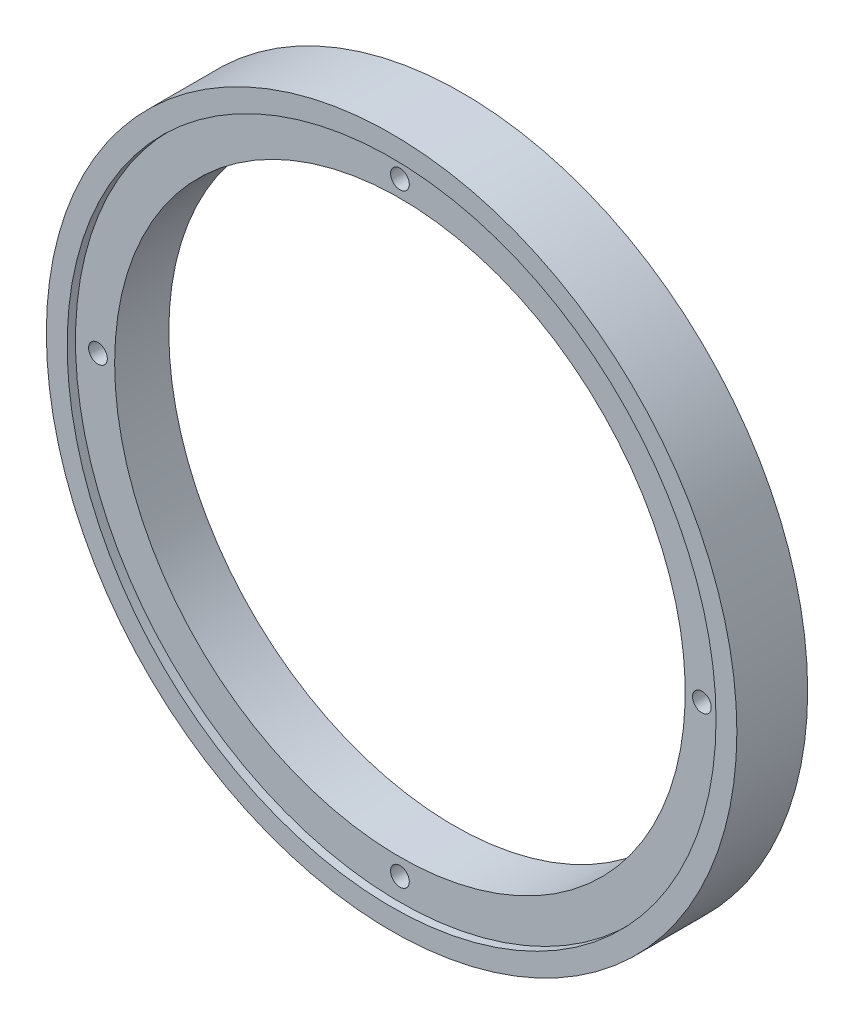
SolidWorks part; units mm, degrees
ref_plane "Plan de face" through (0, 0, 0) normal (0, 0, 1) x (1, 0, 0)
ref_plane "Plan de dessus" through (0, 0, 0) normal (0, 1, 0) x (1, 0, 0)
ref_plane "Plan de droite" through (0, 0, 0) normal (1, 0, 0) x (0, 0, -1)
sketch "Esquisse1" plane through (0, 0, 0) normal (0, 0, 1) x (1, 0, 0)
  line L14 (0, 72.5) -> (0, -72.5) construction
  line L15 (-72.5, 0) -> (72.5, 0) construction
  circle A60 centre (0, 0) radius 77.9
  circle A61 centre (0, 0) radius 72.5 construction
  circle A62 centre (0, 72.5) radius 2.25
  circle A63 centre (72.5, 0) radius 2.25
  circle A64 centre (0, -72.5) radius 2.25
  circle A65 centre (-72.5, 0) radius 2.25
  circle A66 centre (0, 0) radius 68.5
  point P0 (0, 0)
  point P30 (0, 0)
  point P52 (0, 0)
  point P57 (0, 0)
  point P83 (0, 0)
  point P105 (0, 0)
  dimension "D5" = 4.5
  dimension "D3" = 155.8
  dimension "D4" = 145
  dimension "D1" = 137
  dimension "D6" = 4
extrude "Boss.-Extru.1" add sketch "Esquisse1" along normal blind 13 contours A60 A66 A65 A64 A63 A62 region at (-75.6967, 0, 0)
sketch "Esquisse2" plane through (0, 0, 13) normal (0, 0, 1) x (1, 0, 0)
  circle A0 centre (0, 0) radius 82.9
  circle A1 centre (0, 0) radius 77.9
  circle A2 centre (0, 0) radius 77.9
  dimension "D1" = 0
  dimension "D2" = 5
extrude "Boss.-Extru.2" add sketch "Esquisse2" along normal blind 2 and the other way blind 15
